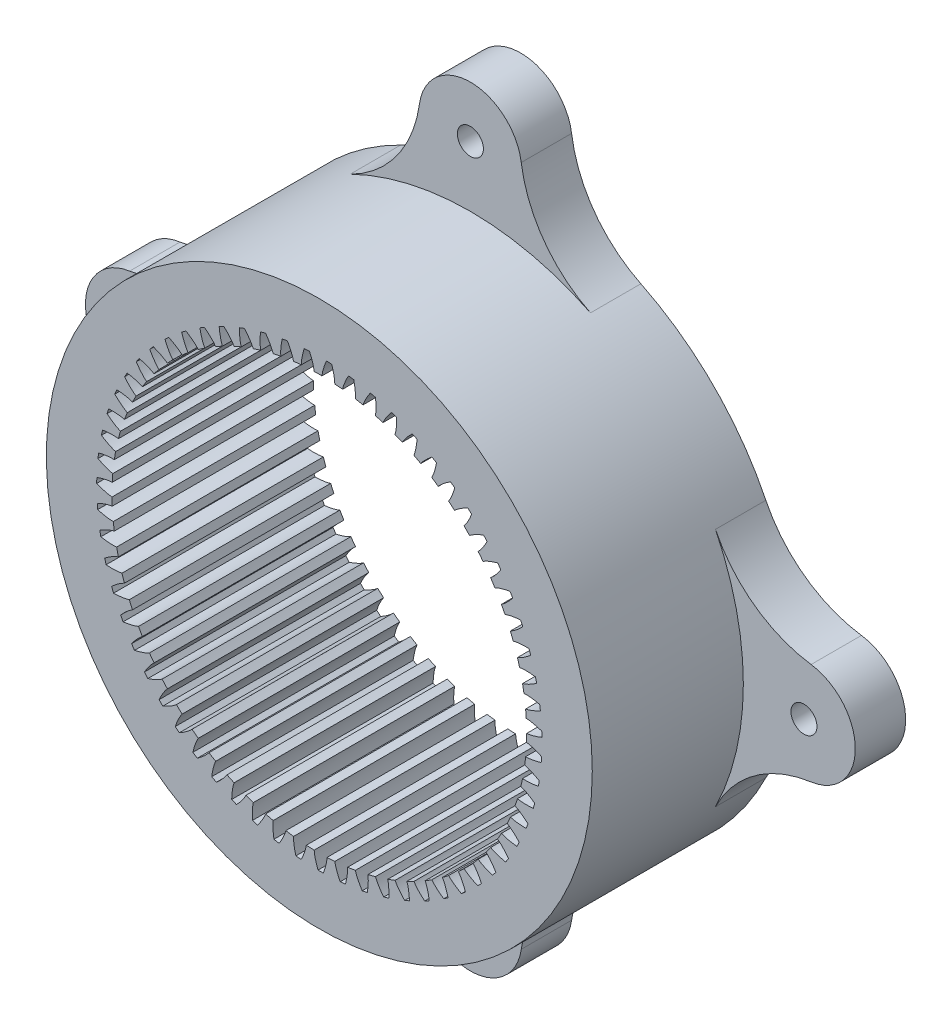
SolidWorks part; units mm, degrees
ref_plane "Front Plane" through (0, 0, 0) normal (0, 0, 1) x (1, 0, 0)
ref_plane "Top Plane" through (0, 0, 0) normal (0, 1, 0) x (1, 0, 0)
ref_plane "Right Plane" through (0, 0, 0) normal (1, 0, 0) x (0, 0, -1)
sketch "Sketch1" plane through (0, 0, 0) normal (0, 0, 1) x (1, 0, 0)
  circle A1 centre (0, 0) radius 32.5275
  dimension "D1" = 65.055
extrude "Boss-Extrude1" add sketch "Sketch1" along normal blind 24
sketch "Sketch2" plane through (0, 0, 24) normal (0, 0, 1) x (1, 0, 0)
  line L0 (0, 0) -> (32.5261, 0.2978) construction
  line L1 (0, 0) -> (32.5012, 1.3085) construction
  line L2 (0, 0) -> (32.4448, 2.318) construction
  line L3 (4.4804, -8.2514) -> (4.4804, -8.182) construction
  circle A0 centre (0, 0) radius 26.5275
  circle A1 centre (0, 0) radius 25.515 construction
  circle A2 centre (0, 0) radius 24.705
  circle A3 centre (0, 0) radius 24.6456 construction
  circle A4 centre (0, 0) radius 32.5275 construction
  spline S0 degree 4 poles (24.6456, 0) (24.6638, 0.0004) (24.7149, 0.0027) (24.8112, 0.0117) (24.9677, 0.033) (25.166, 0.07) (25.4203, 0.129) (25.7171, 0.2126) (26.0397, 0.3193) (26.3862, 0.451) (26.7275, 0.5964) (27.0635, 0.7538) (27.3941, 0.9222) (27.7887, 1.1389) (28.2546, 1.4179) (28.7853, 1.7679) (29.3735, 2.1981) (29.9517, 2.6631) (30.5096, 3.1528) (31.0468, 3.6643) (31.5644, 4.1969) (32.0612, 4.7468) (32.4799, 5.245) (32.8247, 5.6789) (33.107, 6.0515) (33.3225, 6.3445) (33.5448, 6.6589) (33.7402, 6.9423) (34.0132, 7.3554) (34.2081, 7.662) (34.5011, 8.1367) (34.5979, 8.3108) (34.7013, 8.4857) knots 0 0 0 0 0 0.005377 0.015084 0.028532 0.04661 0.064855 0.092111 0.119476 0.146842 0.174209 0.201575 0.228941 0.256307 0.307035 0.361767 0.4165 0.471232 0.525964 0.580697 0.635429 0.690161 0.744894 0.77226 0.799626 0.826992 0.854358 0.881725 0.909091 0.954545 1 1 1 1 1 construction
  spline S1 degree 4 poles (24.6456, 0) (24.6638, 0.0004) (24.7149, 0.0027) (24.8112, 0.0117) (24.9677, 0.033) (25.166, 0.07) (25.4203, 0.129) (25.7171, 0.2126) (26.0397, 0.3193) (26.3862, 0.451) (26.7275, 0.5964) (27.0635, 0.7538) (27.3941, 0.9222) (27.7887, 1.1389) (28.2546, 1.4179) (28.7853, 1.7679) (29.3735, 2.1981) (29.9517, 2.6631) (30.5096, 3.1528) (31.0468, 3.6643) (31.5644, 4.1969) (32.0612, 4.7468) (32.4799, 5.245) (32.8247, 5.6789) (33.107, 6.0515) (33.3225, 6.3445) (33.5448, 6.6589) (33.7402, 6.9423) (33.9159, 7.2082) (34.0091, 7.3515) (34.0546, 7.4225) knots 0 0 0 0 0 0.005377 0.015084 0.028532 0.04661 0.064855 0.092111 0.119476 0.146842 0.174209 0.201575 0.228941 0.256307 0.307035 0.361767 0.4165 0.471232 0.525964 0.580697 0.635429 0.690161 0.744894 0.77226 0.799626 0.826992 0.854358 0.881725 0.909091 0.909091 0.909091 0.909091 0.909091
  spline S2 degree 4 poles (24.598, 1.5311) (24.6162, 1.5319) (24.6673, 1.5328) (24.764, 1.5298) (24.9216, 1.5182) (25.1217, 1.4936) (25.3792, 1.4506) (25.6806, 1.3855) (26.0092, 1.2991) (26.3632, 1.1891) (26.713, 1.0653) (27.0581, 0.929) (27.3985, 0.7814) (27.8058, 0.5897) (28.2881, 0.3402) (28.8396, 0.0238) (29.4533, -0.369) (30.0593, -0.7972) (30.6465, -1.2513) (31.2145, -1.7284) (31.7641, -2.2278) (32.2942, -2.7458) (32.7431, -3.217) (33.1141, -3.6286) (33.419, -3.983) (33.6523, -4.262) (33.8937, -4.562) (34.1063, -4.8328) (34.4044, -5.228) (34.6181, -5.522) (34.9399, -5.9775) (35.0474, -6.1453) (35.1614, -6.3134) knots 0 0 0 0 0 0.005377 0.015084 0.028532 0.04661 0.064855 0.092111 0.119476 0.146842 0.174209 0.201575 0.228941 0.256307 0.307035 0.361767 0.4165 0.471232 0.525964 0.580697 0.635429 0.690161 0.744894 0.77226 0.799626 0.826992 0.854358 0.881725 0.909091 0.954545 1 1 1 1 1 construction
  spline S3 degree 4 poles (24.598, 1.5311) (24.6162, 1.5319) (24.6673, 1.5328) (24.764, 1.5298) (24.9216, 1.5182) (25.1217, 1.4936) (25.3792, 1.4506) (25.6806, 1.3855) (26.0092, 1.2991) (26.3632, 1.1891) (26.713, 1.0653) (27.0581, 0.929) (27.3985, 0.7814) (27.8058, 0.5897) (28.2881, 0.3402) (28.8396, 0.0238) (29.4533, -0.369) (30.0593, -0.7972) (30.6465, -1.2513) (31.2145, -1.7284) (31.7641, -2.2278) (32.2942, -2.7458) (32.7431, -3.217) (33.1141, -3.6286) (33.419, -3.983) (33.6523, -4.262) (33.8937, -4.562) (34.1063, -4.8328) (34.2982, -5.0872) (34.4001, -5.2245) (34.45, -5.2925) knots 0 0 0 0 0 0.005377 0.015084 0.028532 0.04661 0.064855 0.092111 0.119476 0.146842 0.174209 0.201575 0.228941 0.256307 0.307035 0.361767 0.4165 0.471232 0.525964 0.580697 0.635429 0.690161 0.744894 0.77226 0.799626 0.826992 0.854358 0.881725 0.909091 0.909091 0.909091 0.909091 0.909091
  point P6 (31.075, 3.9378)
  point P7 (0, 0)
  point P8 (0, 0)
  point P9 (35.3477, 2.9197)
  point P12 (0, 0)
  point P13 (0, 0)
  point P14 (22.9625, 1.852)
  point P15 (0, 0)
  point P16 (29.3471, 0)
  point P18 (20.4829, 0.0887)
  point P22 (0, 0)
  point P23 (0, 0)
  point P24 (0, 0)
  point P25 (0, 0)
  point P26 (20.3831, 0)
  point P27 (0, 0)
  point P28 (0, 0)
  point P29 (0, 0)
  point P30 (20.3913, 0)
  point P31 (0, 0)
  point P32 (0, 0)
  point P33 (20.3913, 0)
  point P34 (0, 0)
  point P35 (0, 0)
  point P36 (0, 0)
  point P38 (20.3253, 1.6393)
  point P39 (20.3253, 1.6393)
  point P40 (0, 0)
  point P41 (0, 0)
  point P42 (0, 0)
  point P43 (29.2521, 2.3593)
  point P44 (22.5567, 0.9082)
  point P45 (22.5567, 0.9082)
  point P46 (0, 0)
  point P47 (29.3233, 1.1806)
  point P48 (31.3936, 5.9909)
  point P49 (8.7539, 2.4233)
  point P53 (20.3913, 0)
  point P54 (0, 0)
  point P55 (0, 0)
  point P56 (20.9997, 0.1199)
  point P57 (0, 0)
  point P58 (21, 0)
  point P59 (0, 0)
  point P60 (20.3913, 0)
  point P61 (0, 0)
  point P62 (0, 0)
  point P64 (29.0567, 6.1816)
  dimension "D5" = 1.781
  dimension "D6" = 1.781
sketch "Sketch5" plane through (0, 0, 24) normal (0, 0, 1) x (1, 0, 0)
  circle A0 centre (0, 0) radius 24.705 construction
  circle A1 centre (0, 0) radius 24.705
extrude "Cut-Extrude1" cut sketch "Sketch5" against normal through all
sketch "Sketch6" plane through (0, 0, 24) normal (0, 0, 1) x (1, 0, 0)
  circle A0 centre (0, 0) radius 26.5275 construction
  arc A1 (26.5226, 0.5105) -> (26.5031, 1.1383) centre (0, 0) ccw
  spline S0 degree 4 poles (81.8704, -996.7756) (22.1231, -19.3537) (22.2577, 0.9901) (23.5811, 1.6169) (24.9216, 1.5182) (25.1217, 1.4936) (25.3792, 1.4506) (25.6806, 1.3855) (26.0092, 1.2991) (26.3632, 1.1891) (26.713, 1.0653) (27.0581, 0.929) (27.3985, 0.7814) (27.8058, 0.5897) (28.2881, 0.3402) (28.8396, 0.0238) (29.4533, -0.369) (30.0593, -0.7972) (30.6465, -1.2513) (31.2145, -1.7284) (31.7641, -2.2278) (32.2942, -2.7458) (32.7431, -3.217) (33.1141, -3.6286) (33.419, -3.983) (33.6523, -4.262) (33.8937, -4.562) (34.8989, -5.8417) (37.0043, -8.8837) (15.6084, 19.9162) (625.4785, -811.859) knots -0.349933 -0.349933 -0.349933 -0.349933 -0.349933 0.005377 0.015084 0.028532 0.04661 0.064855 0.092111 0.119476 0.146842 0.174209 0.201575 0.228941 0.256307 0.307035 0.361767 0.4165 0.471232 0.525964 0.580697 0.635429 0.690161 0.744894 0.77226 0.799626 0.826992 0.854358 0.881725 1.317024 1.317024 1.317024 1.317024 1.317024 only from (24.598, 1.5311) to (34.45, -5.2925) construction
  spline S1 degree 4 poles (19.7865, 999.9364) (20.878, 20.6907) (22.2762, 0.3946) (23.636, -0.1488) (24.9677, 0.033) (25.166, 0.07) (25.4203, 0.129) (25.7171, 0.2126) (26.0397, 0.3193) (26.3862, 0.451) (26.7275, 0.5964) (27.0635, 0.7538) (27.3941, 0.9222) (27.7887, 1.1389) (28.2546, 1.4179) (28.7853, 1.7679) (29.3735, 2.1981) (29.9517, 2.6631) (30.5096, 3.1528) (31.0468, 3.6643) (31.5644, 4.1969) (32.0612, 4.7468) (32.4799, 5.245) (32.8247, 5.6789) (33.107, 6.0515) (33.3225, 6.3445) (33.5448, 6.6589) (34.4686, 7.9986) (36.3809, 11.1655) (16.8155, -18.9081) (573.8327, 849.1492) knots -0.349933 -0.349933 -0.349933 -0.349933 -0.349933 0.005377 0.015084 0.028532 0.04661 0.064855 0.092111 0.119476 0.146842 0.174209 0.201575 0.228941 0.256307 0.307035 0.361767 0.4165 0.471232 0.525964 0.580697 0.635429 0.690161 0.744894 0.77226 0.799626 0.826992 0.854358 0.881725 1.317024 1.317024 1.317024 1.317024 1.317024 only from (24.6456, 0) to (34.0546, 7.4225) construction
  spline S2 degree 4 poles (24.598, 1.5311) (24.6162, 1.5319) (24.6673, 1.5328) (24.764, 1.5298) (24.9216, 1.5182) (25.1217, 1.4936) (25.3792, 1.4506) (25.6806, 1.3855) (26.0003, 1.3014) (26.2571, 1.2221) (26.4242, 1.1658) (26.5031, 1.1383) knots 0 0 0 0 0 0.005377 0.015084 0.028532 0.04661 0.064855 0.092111 0.119476 0.144134 0.144134 0.144134 0.144134 0.144134
  spline S3 degree 4 poles (24.6456, 0) (24.6638, 0.0004) (24.7149, 0.0027) (24.8112, 0.0117) (24.9677, 0.033) (25.166, 0.07) (25.4203, 0.129) (25.7171, 0.2126) (26.031, 0.3164) (26.2823, 0.4115) (26.4456, 0.4781) (26.5226, 0.5105) knots 0 0 0 0 0 0.005377 0.015084 0.028532 0.04661 0.064855 0.092111 0.119476 0.144134 0.144134 0.144134 0.144134 0.144134
extrude "Cut-Extrude2" cut sketch "Sketch6" against normal through all and the other way through all
pattern_circular "CirPattern2" count 63 over 360 about axis through (0, 0, 24) along (0, 0, -1) of "Cut-Extrude2"
sketch "Sketch7" plane through (0, 0, 0) normal (0, 0, 1) x (1, 0, 0)
  line L0 (0, 0) -> (-39.75, 0) construction
  line L1 (-39.75, 6.1201) -> (-31.9466, 6.1201)
  line L2 (-39.75, -6.1201) -> (-31.9466, -6.1201)
  circle A2 centre (-39.75, 0) radius 1.55
  arc A3 (-39.75, 6.1201) -> (-39.75, -6.1201) centre (-39.75, 0) ccw
  circle A5 centre (0, 0) radius 32.5275 construction
  arc A6 (-31.9466, 6.1201) -> (-31.9466, -6.1201) centre (0, 0) ccw
  dimension "D2" = 3.1
  dimension "D3" = 12.2403
  dimension "D1" = 39.75
extrude "Boss-Extrude3" add sketch "Sketch7" along normal blind 6
fillet "Fillet1" radius 15 2 edges at (-31.9466, 6.1201, 3) (-31.9466, -6.1201, 3)
pattern_circular "CirPattern5" count 4 over 360 about axis through (0, 0, 0) along (0, 0, 1) of "Fillet1", "Boss-Extrude3"
equation "\"P`\"= \"N\" / \"dp\"'Diametral pitch - number of teeth per mm"
equation "\"N\" = 63'# of teeth"
equation "\"phi\"= 15deg'Pressure angle"
equation "\"a\"= 1 / \"P`\"'Addendum"
equation "\"b\"= 1.25 / \"P`\"'Dedendum"
equation "\"c\"= \"b\" - \"a\"'clearance"
equation "\"dp\"= \"dp_from_mod\"'pitch cirle diameter"
equation "\"db\"= \"dp\" * cos ( \"phi\" )'base circle diameter"
equation "\"alpha\"= sqr ( \"dp\" ^ 2 - \"db\" ^ 2 ) / \"db\" * 180 / pi - \"phi\""
equation "\"D3@Sketch2\"= \"dp\"'Pitch circle dia"
equation "\"D4@Sketch2\"= \"dp\" - 2 * \"a\"'Tip circle (addendum) dia"
equation "\"D2@Sketch2\"= \"dp\" + 2 * \"b\"'Root circle (dedendum) dia"
equation "\"D1@Sketch2\"= \"db\""
equation "\"mod\"= 0.81mm'module - gear thickness"
equation "\"dp_from_mod\"= \"N\" * \"mod\""
equation "\"D5@Sketch2\" = 360 / ( 4 * \"N\" ) + \"alpha\""
equation "\"D6@Sketch2\"= 360 / ( 4 * \"N\" ) + \"alpha\""
equation "\"t_start\"= sqr ( ( \"AddendumDia\" / 2 ) ^ 2 - ( \"db\" / 2 ) ^ 2 ) / ( \"db\" / 2 )"
equation "\"AddendumDia\"= \"dp\" - 2 * \"a\""
equation "\"DedendumDia\"= \"dp\" + 2 * \"b\""
equation "\"D7@Sketch2\" = \"t_start\""
equation "\"D1@Sketch1\"= \"dp\" + 2 * \"b\" + 12mm"
